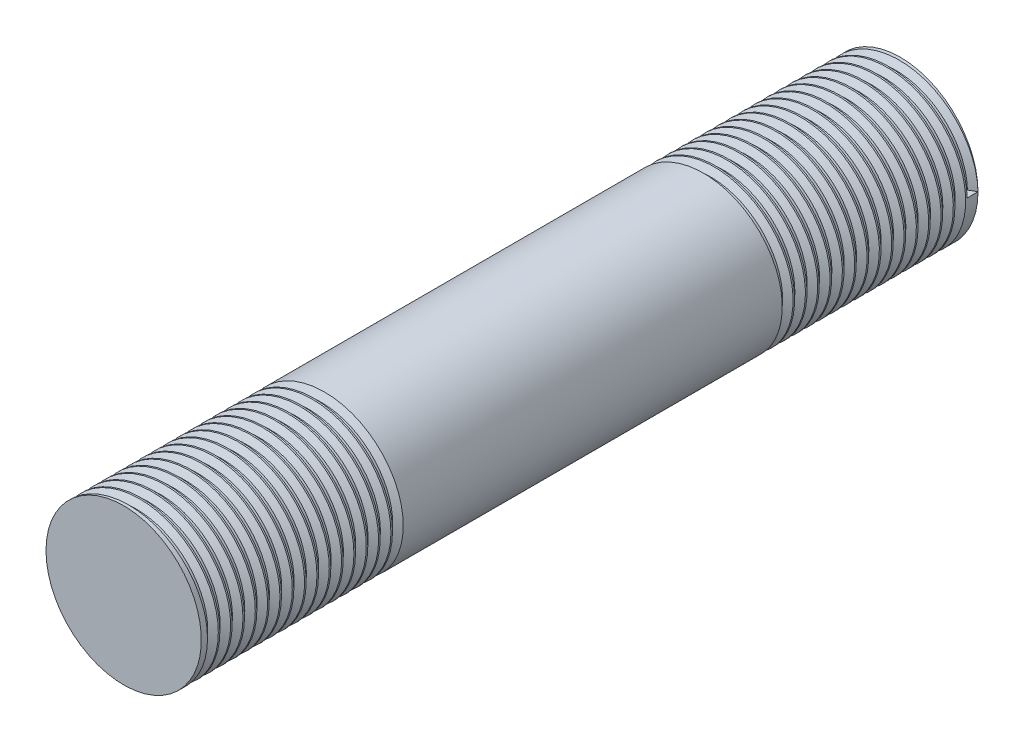
SolidWorks part; units mm, degrees
ref_plane "前视基准面" through (0, 0, 0) normal (0, 0, 1) x (1, 0, 0)
ref_plane "上视基准面" through (0, 0, 0) normal (0, 1, 0) x (1, 0, 0)
ref_plane "右视基准面" through (0, 0, 0) normal (1, 0, 0) x (0, 0, -1)
sketch "草图1" plane through (0, 0, 0) normal (0, 0, 1) x (1, 0, 0)
  circle A0 centre (0, 0) radius 2
extrude "凸台-拉伸1" add sketch "草图1" along normal blind 20
thread "螺纹线8" pitch 0.3175 method cut profile "螺纹线轮廓8" start angle 0, offset 0, length 5, pitch 0.3175, diameter 4
ref_plane "基准面8" through (2, 0, 0) normal (0, -1, 0) x (1, 0, 0)
sketch "螺纹线轮廓8" plane through (2, 0, 0) normal (0, -1, 0) x (1, 0, 0)
  line L0 (0, 0) -> (0, 0.3175) construction
  line L11 (0, 0) -> (0, 0.2778)
  line L12 (0, 0.2778) -> (-0.1719, 0.1786)
  line L13 (-0.1719, 0.1786) -> (-0.1719, 0.0992)
  line L15 (-0.1719, 0.0992) -> (0, 0)
  line L17 (-0.1719, 0.1389) -> (0, 0.1389) construction
  point P2 (0, 0)
  dimension "Pitch" = 0.3175
  dimension "Profile_Angle" = 60
  dimension "Profile_Land" = 0.0794
  dimension "Profile_Height" = 0.1719
thread "螺纹线9" pitch 0.3175 method cut profile "螺纹线轮廓9" start angle 0, offset 0, length 5, pitch 0.3175, diameter 4
ref_plane "基准面9" through (-2, 0, 20) normal (0, -1, 0) x (-1, 0, 0)
sketch "螺纹线轮廓9" plane through (-2, 0, 20) normal (0, -1, 0) x (-1, 0, 0)
  line L0 (0, 0) -> (0, 0.3175) construction
  line L11 (0, 0) -> (0, 0.2778)
  line L12 (0, 0.2778) -> (-0.1719, 0.1786)
  line L13 (-0.1719, 0.1786) -> (-0.1719, 0.0992)
  line L15 (-0.1719, 0.0992) -> (0, 0)
  line L17 (-0.1719, 0.1389) -> (0, 0.1389) construction
  point P2 (0, 0)
  dimension "Pitch" = 0.3175
  dimension "Profile_Angle" = 60
  dimension "Profile_Land" = 0.0794
  dimension "Profile_Height" = 0.1719
